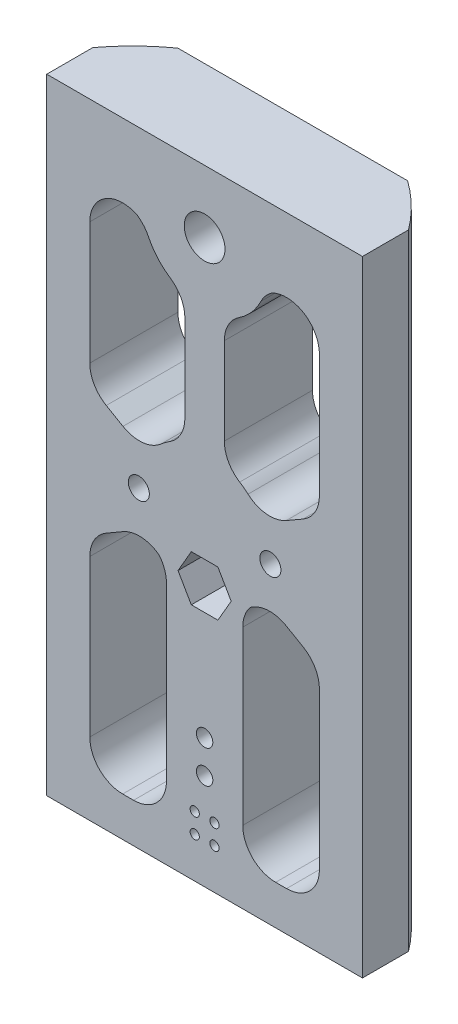
SolidWorks part; units mm, degrees
ref_plane "Front Plane" through (0, 0, 0) normal (0, 0, 1) x (1, 0, 0)
ref_plane "Top Plane" through (0, 0, 0) normal (0, 1, 0) x (1, 0, 0)
ref_plane "Right Plane" through (0, 0, 0) normal (1, 0, 0) x (0, 0, -1)
sketch "Sketch1" plane through (0, 0, 0) normal (0, 0, 1) x (1, 0, 0)
  line L0 (-2.275, -128.15) -> (-2.275, -128.6)
  line L1 (2.275, -128.15) -> (2.275, -128.6)
  line L2 (-2.275, -133.15) -> (-2.275, -134.025)
  line L3 (2.275, -133.15) -> (2.275, -134.025)
  line L11 (-2.275, -128.15) -> (2.275, -128.15)
  line L12 (2.275, -128.15) -> (2.275, -123.6)
  line L13 (2.275, -123.6) -> (-2.275, -123.6)
  line L14 (-2.275, -123.6) -> (-2.275, -128.15)
  line L15 (-2.275, -128.15) -> (2.275, -128.15)
  line L16 (2.275, -128.15) -> (2.275, -123.6)
  line L17 (2.275, -123.6) -> (-2.275, -123.6)
  line L18 (-2.275, -123.6) -> (-2.275, -128.15)
  line L24 (-2.275, -133.15) -> (2.275, -133.15)
  line L25 (2.275, -133.15) -> (2.275, -128.6)
  line L26 (2.275, -128.6) -> (-2.275, -128.6)
  line L27 (-2.275, -128.6) -> (-2.275, -133.15)
  line L28 (-2.275, -133.15) -> (2.275, -133.15)
  line L29 (2.275, -133.15) -> (2.275, -128.6)
  line L30 (2.275, -128.6) -> (-2.275, -128.6)
  line L31 (-2.275, -128.6) -> (-2.275, -133.15)
  line L37 (0, -123.6) -> (0, -142.4) construction
  line L39 (7, -120.5) -> (-7, -120.5)
  line L40 (7, -120.5) -> (7, -145.5)
  line L41 (7, -145.5) -> (-7, -145.5)
  line L42 (-7, -120.5) -> (-7, -145.5)
  line L43 (7, -120.5) -> (-7, -145.5) construction
  line L44 (7, -145.5) -> (-7, -120.5) construction
  line L45 (-1, -142.4) -> (1, -142.4)
  line L46 (1, -142.4) -> (1, -141.625)
  line L47 (1, -141.625) -> (3.8, -141.625)
  line L48 (3.8, -141.625) -> (3.8, -134.025)
  line L49 (3.8, -134.025) -> (-3.8, -134.025)
  line L50 (-3.8, -134.025) -> (-3.8, -141.625)
  line L51 (-3.8, -141.625) -> (-1, -141.625)
  line L52 (-1, -141.625) -> (-1, -142.4)
  line L53 (-1, -142.4) -> (1, -142.4)
  line L54 (1, -142.4) -> (1, -141.625)
  line L55 (1, -141.625) -> (3.8, -141.625)
  line L56 (3.8, -141.625) -> (3.8, -134.025)
  line L57 (3.8, -134.025) -> (-3.8, -134.025)
  line L58 (-3.8, -134.025) -> (-3.8, -141.625)
  line L59 (-3.8, -141.625) -> (-1, -141.625)
  line L60 (-1, -141.625) -> (-1, -142.4)
  circle A0 centre (0, -125.875) radius 1.275
  circle A1 centre (0, -130.875) radius 1.275
  circle A2 centre (-1.5, -139.325) radius 0.65
  circle A3 centre (-1.5, -136.325) radius 0.65
  circle A4 centre (1.5, -136.325) radius 0.65
  circle A5 centre (1.5, -139.325) radius 0.65
  point P25 (0, -133)
  dimension "D4" = 2.55
  dimension "D5" = 1.3
  dimension "D6" = 25
  dimension "D7" = 14
  dimension "D1" = 0.2
  dimension "D2" = 0.2
  dimension "D3" = 0.2
extrude "Boss-Extrude1" add sketch "Sketch1" against normal blind 6.4
sketch "Sketch3" plane through (0, 0, 0) normal (0, 0, 1) x (1, 0, 0)
  line L4 (7, -120.5) -> (-7, -120.5)
  line L5 (-7, -120.5) -> (-7, -145.5)
  line L6 (-7, -145.5) -> (7, -145.5)
  line L7 (7, -145.5) -> (7, -120.5)
  line L8 (7, -120.5) -> (-7, -120.5)
  line L9 (-7, -120.5) -> (-7, -145.5)
  line L10 (-7, -145.5) -> (7, -145.5)
  line L11 (7, -145.5) -> (7, -120.5)
  circle A0 centre (-1.5, -139.325) radius 0.7
  circle A1 centre (-1.5, -136.325) radius 0.7
  circle A2 centre (1.5, -136.325) radius 0.7
  circle A3 centre (1.5, -139.325) radius 0.7
  circle A4 centre (0, -130.875) radius 1.25
  circle A5 centre (0, -125.875) radius 1.25
  dimension "D2" = 2.5
  dimension "D3" = 1.4
  dimension "D1" = 0
extrude "Boss-Extrude3" add sketch "Sketch3" along normal blind 7
sketch "Sketch4" plane through (0, -145.5, 0) normal (0, -1, 0) x (1, 0, 0)
  line L0 (-7, -6.4) -> (-17.4539, -6.4)
  line L1 (-7, 7) -> (-27.9106, 7)
  line L2 (7, -6.4) -> (17.4539, -6.4)
  line L3 (7, 7) -> (27.9106, 7)
  line L4 (-24, 0) -> (-24, 7)
  line L5 (24, 0) -> (24, 7)
  circle A4 centre (0, 18) radius 30
  arc A5 (-24, 0) -> (24, 0) centre (0, 18) ccw construction
  line M2 (7, -6.4) -> (7, 7)
  line M4 (-7, 7) -> (-7, -6.4)
extrude "Boss-Extrude4" add sketch "Sketch4" against normal up to surface (25 mm away) contours L1 A4 L0 M4 | L2 A4 L3 M2
sketch "Sketch5" plane through (0, -120.5, 0) normal (0, 1, 0) x (1, 0, 0)
  line L2 (17.4539, 6.4) -> (-17.4539, 6.4)
  line L3 (-24, -7) -> (24, -7)
  line L4 (17.4539, 6.4) -> (-17.4539, 6.4)
  line L5 (-24, -7) -> (24, -7)
  line L8 (-24, 0) -> (-24, -7)
  line L9 (-24, 0) -> (-24, -7)
  line L10 (24, -7) -> (24, 0)
  line L11 (24, -7) -> (24, 0)
  arc A2 (-17.4539, 6.4) -> (-24, 0) centre (0, -18) ccw
  arc A3 (24, 0) -> (17.4539, 6.4) centre (0, -18) ccw
  arc A4 (-17.4539, 6.4) -> (-24, 0) centre (0, -18) ccw
  arc A5 (24, 0) -> (17.4539, 6.4) centre (0, -18) ccw
  dimension "D1" = 0
extrude "Boss-Extrude5" add sketch "Sketch5" along normal blind 70
sketch "Sketch6" plane through (0, 0, 7) normal (0, 0, 1) x (1, 0, 0)
  line L0 (0, -50.5) -> (0, -145.5) construction
  line L1 (-24, -50.5) -> (24, -50.5) construction
  line L2 (-24, -145.5) -> (24, -145.5) construction
  circle A0 centre (0, -105.875) radius 2.25
  circle A3 centre (0, -105.875) radius 2.25 construction
  dimension "D2" = 4.5
extrude "Cut-Extrude1" cut sketch "Sketch6" against normal up to next
sketch "Sketch7" plane through (0, 0, 7) normal (0, 0, 1) x (1, 0, 0)
  line L1 (4.0415, -105.875) -> (2.0207, -102.375)
  line L2 (2.0207, -102.375) -> (-2.0207, -102.375)
  line L3 (-2.0207, -102.375) -> (-4.0415, -105.875)
  line L4 (-4.0415, -105.875) -> (-2.0207, -109.375)
  line L5 (-2.0207, -109.375) -> (2.0207, -109.375)
  line L6 (2.0207, -109.375) -> (4.0415, -105.875)
  circle A0 centre (0, -105.875) radius 3.5 construction
  dimension "D1" = 7
extrude "Cut-Extrude2" cut sketch "Sketch7" against normal offset from surface (7.4 mm away) 6 up to face at (2.25, -105.875, -6.4)
sketch "Sketch9" plane through (0, 0, -6.4) normal (0, 0, -1) x (-1, 0, 0)
  line L0 (-24, -98) -> (24, -98) construction
  line L1 (-24, -50.5) -> (-24, -145.5) construction
  line L2 (24, -50.5) -> (24, -145.5) construction
  line L3 (0, -50.5) -> (0, -145.5) construction
  line L4 (-17.4539, -50.5) -> (17.4539, -50.5) construction
  line L5 (-17.4539, -145.5) -> (17.4539, -145.5) construction
  circle A0 centre (-10, -98) radius 1.6
  circle A1 centre (10, -98) radius 1.6
  dimension "D1" = 3.2
  dimension "D2" = 20
extrude "Cut-Extrude4" cut sketch "Sketch9" against normal up to next
sketch "Sketch10" plane through (0, 0, -6.4) normal (0, 0, -1) x (-1, 0, 0)
  line L0 (0, -50.5) -> (0, -145.5) construction
  line L1 (-10, -101.2332) -> (-7.2, -99.6166)
  line L2 (-7.2, -99.6166) -> (-7.2, -96.3834)
  line L3 (-7.2, -96.3834) -> (-10, -94.7668)
  line L4 (-10, -94.7668) -> (-12.8, -96.3834)
  line L5 (-12.8, -96.3834) -> (-12.8, -99.6166)
  line L6 (-12.8, -99.6166) -> (-10, -101.2332)
  line L7 (-17.4539, -50.5) -> (17.4539, -50.5) construction
  line L8 (-17.4539, -145.5) -> (17.4539, -145.5) construction
  line L9 (12.8, -99.6166) -> (10, -101.2332)
  line L10 (12.8, -96.3834) -> (12.8, -99.6166)
  line L11 (10, -94.7668) -> (12.8, -96.3834)
  line L12 (7.2, -96.3834) -> (10, -94.7668)
  line L13 (7.2, -99.6166) -> (7.2, -96.3834)
  line L14 (10, -101.2332) -> (7.2, -99.6166)
  circle A0 centre (-10, -98) radius 2.8 construction
  dimension "D1" = 5.6
extrude "Cut-Extrude5" cut sketch "Sketch10" against normal offset from surface (7.4 mm away) 6 up to face at (11.6, -98, 7)
sketch "Sketch11" plane through (0, 0, 7) normal (0, 0, 1) x (1, 0, 0)
  line L0 (0, -50.5) -> (0, -145.5) construction
  line L1 (-24, -50.5) -> (24, -50.5) construction
  line L2 (-24, -145.5) -> (24, -145.5) construction
  circle A0 centre (0, -60) radius 3.1
  circle A1 centre (0, -60) radius 9.5
  dimension "D1" = 19
  dimension "D2" = 6.2
extrude "Cut-Extrude6" cut sketch "Sketch11" against normal up to next contours A0
sketch "Sketch12" plane through (0, 0, -6.4) normal (0, 0, -1) x (-1, 0, 0)
  line L1 (0, -54.2265) -> (-5, -57.1132)
  line L2 (-5, -57.1132) -> (-5, -62.8868)
  line L3 (-5, -62.8868) -> (0, -65.7735)
  line L4 (0, -65.7735) -> (5, -62.8868)
  line L5 (5, -62.8868) -> (5, -57.1132)
  line L6 (5, -57.1132) -> (0, -54.2265)
  circle A0 centre (0, -60) radius 5 construction
  dimension "D1" = 10
extrude "Cut-Extrude7" cut sketch "Sketch12" against normal blind 6
sketch "Sketch13" plane through (0, 0, -6.4) normal (0, 0, -1) x (-1, 0, 0)
  line L0 (-7, -64.0415) -> (-17.4539, -58.0059)
  line L1 (-3, -68.0829) -> (-3, -66.3509)
  line L2 (-3, -96.4989) -> (-17.4539, -88.1539)
  line L3 (3, -68.0829) -> (3, -66.3509)
  line L4 (7, -64.0415) -> (17.4539, -58.0059)
  line L5 (3, -96.4989) -> (17.4539, -88.1539)
  line L6 (-3, -99.5011) -> (-17.4539, -107.8461)
  line L7 (3, -99.5011) -> (17.4539, -107.8461)
  line L8 (17.4539, -145.5) -> (17.4539, -50.5)
  line L9 (17.4539, -50.5) -> (-17.4539, -50.5)
  line L10 (-17.4539, -50.5) -> (-17.4539, -145.5)
  line L11 (-17.4539, -145.5) -> (17.4539, -145.5)
  line L12 (17.4539, -145.5) -> (17.4539, -50.5)
  line L13 (17.4539, -50.5) -> (-17.4539, -50.5)
  line L14 (-17.4539, -50.5) -> (-17.4539, -145.5)
  line L15 (-17.4539, -145.5) -> (17.4539, -145.5)
  line L16 (-17.4539, -139.5) -> (17.4539, -139.5)
  line L17 (-5.2, -98) -> (5.2, -98) construction
  line L18 (-5.8, -132.025) -> (-5.8, -106.1462)
  line L19 (5.8, -132.025) -> (5.8, -106.1462)
  line L32 (0, -68.0829) -> (0, -121.6) construction
  line L33 (-3, -68.0829) -> (-3, -121.6)
  line L34 (3, -68.0829) -> (3, -121.6)
  line L37 (3, -144.4) -> (3, -143.625)
  line L38 (3, -143.625) -> (5.8, -143.625)
  line L39 (5.8, -143.625) -> (5.8, -132.025)
  line L40 (5.8, -132.025) -> (4.275, -132.025)
  line L41 (4.275, -132.025) -> (4.275, -121.6)
  line L42 (4.275, -121.6) -> (-4.275, -121.6)
  line L43 (-4.275, -121.6) -> (-4.275, -132.025)
  line L44 (-4.275, -132.025) -> (-5.8, -132.025)
  line L45 (-5.8, -132.025) -> (-5.8, -143.625)
  line L46 (-5.8, -143.625) -> (-3, -143.625)
  line L47 (-3, -143.625) -> (-3, -144.4)
  line L48 (-3, -144.4) -> (3, -144.4)
  line L49 (3, -144.4) -> (3, -143.625)
  line L50 (3, -143.625) -> (5.8, -143.625)
  line L51 (5.8, -143.625) -> (5.8, -132.025)
  line L52 (5.8, -132.025) -> (4.275, -132.025)
  line L53 (4.275, -132.025) -> (4.275, -121.6)
  line L54 (4.275, -121.6) -> (-4.275, -121.6)
  line L55 (-4.275, -121.6) -> (-4.275, -132.025)
  line L56 (-4.275, -132.025) -> (-5.8, -132.025)
  line L57 (-5.8, -132.025) -> (-5.8, -143.625)
  line L58 (-5.8, -143.625) -> (-3, -143.625)
  line L59 (-3, -143.625) -> (-3, -144.4)
  line L60 (-3, -144.4) -> (3, -144.4)
  line L62 (0, -51.9171) -> (-7, -55.9585)
  line L63 (7, -55.9585) -> (0, -51.9171)
  line L64 (7, -64.0415) -> (7, -55.9585)
  line L65 (0, -68.0829) -> (7, -64.0415)
  line L66 (-7, -64.0415) -> (0, -68.0829)
  line L67 (-7, -55.9585) -> (-7, -64.0415)
  line L68 (0, -51.9171) -> (-7, -55.9585)
  line L69 (7, -55.9585) -> (0, -51.9171)
  line L70 (7, -64.0415) -> (7, -55.9585)
  line L71 (0, -68.0829) -> (7, -64.0415)
  line L72 (-7, -64.0415) -> (0, -68.0829)
  line L73 (-7, -55.9585) -> (-7, -64.0415)
  line L83 (-14.8, -100.7713) -> (-10, -103.5426)
  line L84 (-10, -103.5426) -> (-5.2, -100.7713)
  line L85 (-5.2, -100.7713) -> (-5.2, -95.2287)
  line L86 (-5.2, -95.2287) -> (-10, -92.4574)
  line L87 (-10, -92.4574) -> (-14.8, -95.2287)
  line L88 (-14.8, -95.2287) -> (-14.8, -100.7713)
  line L89 (-14.8, -100.7713) -> (-10, -103.5426)
  line L90 (-10, -103.5426) -> (-5.2, -100.7713)
  line L91 (-5.2, -100.7713) -> (-5.2, -95.2287)
  line L92 (-5.2, -95.2287) -> (-10, -92.4574)
  line L93 (-10, -92.4574) -> (-14.8, -95.2287)
  line L94 (-14.8, -95.2287) -> (-14.8, -100.7713)
  line L95 (-10.8, -98.4619) -> (-10, -98.9238)
  line L96 (-10, -98.9238) -> (-9.2, -98.4619)
  line L97 (-9.2, -98.4619) -> (-9.2, -97.5381)
  line L98 (-9.2, -97.5381) -> (-10, -97.0762)
  line L99 (-10, -97.0762) -> (-10.8, -97.5381)
  line L100 (-10.8, -97.5381) -> (-10.8, -98.4619)
  line L101 (-10.8, -98.4619) -> (-10, -98.9238)
  line L102 (-10, -98.9238) -> (-9.2, -98.4619)
  line L103 (-9.2, -98.4619) -> (-9.2, -97.5381)
  line L104 (-9.2, -97.5381) -> (-10, -97.0762)
  line L105 (-10, -97.0762) -> (-10.8, -97.5381)
  line L106 (-10.8, -97.5381) -> (-10.8, -98.4619)
  line L114 (10, -92.4574) -> (5.2, -95.2287)
  line L115 (14.8, -95.2287) -> (10, -92.4574)
  line L116 (14.8, -100.7713) -> (14.8, -95.2287)
  line L117 (10, -103.5426) -> (14.8, -100.7713)
  line L118 (5.2, -100.7713) -> (10, -103.5426)
  line L119 (5.2, -95.2287) -> (5.2, -100.7713)
  line L120 (10, -92.4574) -> (5.2, -95.2287)
  line L121 (14.8, -95.2287) -> (10, -92.4574)
  line L122 (14.8, -100.7713) -> (14.8, -95.2287)
  line L123 (10, -103.5426) -> (14.8, -100.7713)
  line L124 (5.2, -100.7713) -> (10, -103.5426)
  line L125 (5.2, -95.2287) -> (5.2, -100.7713)
  line L126 (10, -97.0762) -> (9.2, -97.5381)
  line L127 (10.8, -97.5381) -> (10, -97.0762)
  line L128 (10.8, -98.4619) -> (10.8, -97.5381)
  line L129 (10, -98.9238) -> (10.8, -98.4619)
  line L130 (9.2, -98.4619) -> (10, -98.9238)
  line L131 (9.2, -97.5381) -> (9.2, -98.4619)
  line L132 (10, -97.0762) -> (9.2, -97.5381)
  line L133 (10.8, -97.5381) -> (10, -97.0762)
  line L134 (10.8, -98.4619) -> (10.8, -97.5381)
  line L135 (10, -98.9238) -> (10.8, -98.4619)
  line L136 (9.2, -98.4619) -> (10, -98.9238)
  line L137 (9.2, -97.5381) -> (9.2, -98.4619)
  circle A0 centre (0, -98) radius 10
  circle A1 centre (0, -60) radius 9.5
  circle M74 centre (0, -105.875) radius 2.25
  line M87 (17.4539, -145.5) -> (17.4539, -50.5)
  line M89 (-17.4539, -50.5) -> (-17.4539, -145.5)
  dimension "D11" = 19
  dimension "D10" = 6
  dimension "D1" = 0
  dimension "D2" = 2
  dimension "D3" = 2
  dimension "D4" = 3
  dimension "D5" = 3
  dimension "D6" = 2
  dimension "D7" = 2
  dimension "D8" = 2
  dimension "D9" = 2
extrude "Cut-Extrude8" cut sketch "Sketch13" against normal up to next contours L72 L0 L2 L33 L1 M89 | L57 L56 L55 L54 L33 L6 L16 M74 M89 | L54 L53 L52 L51 L16 L12 L7 L34 M74 | A1 L34 A0 L120 L5 L4 M87
fillet "Fillet1" radius 5 22 edges at (5.8, -106.1462, 0.3) (8.7585, -102.8258, 0.3) (17.4539, -107.8461, 0.3) (17.4539, -139.5, 0.3) (5.8, -139.5, 0.3) (-17.4539, -139.5, 0.3) (-5.8, -139.5, 0.3) (-5.8, -106.1462, 0.3) (-8.7585, -102.8258, 0.3) (-17.4539, -107.8461, 0.3) (-17.4539, -58.0059, 0.3) (-17.4539, -88.1539, 0.3) (-8.7585, -93.1742, 0.3) (-3, -88.4606, 0.3) (8.7585, -93.1742, 0.3) (17.4539, -88.1539, 0.3) (-9.0621, -62.8509, 0.3) (-3, -69.0139, 0.3) (3, -88.4606, 0.3) (3, -69.0139, 0.3) (9.0621, -62.8509, 0.3) (17.4539, -58.0059, 0.3)
